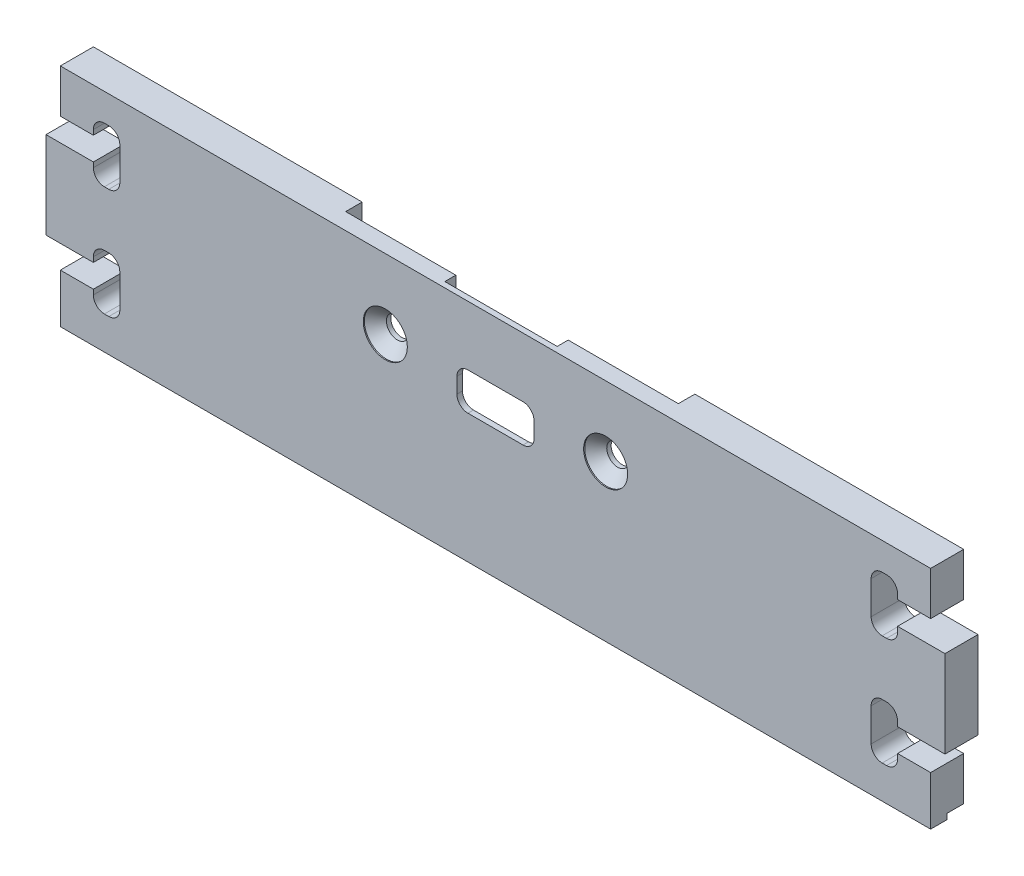
SolidWorks part; units mm, degrees
ref_plane "Front Plane" through (0, 0, 0) normal (0, 0, 1) x (1, 0, 0)
ref_plane "Top Plane" through (0, 0, 0) normal (0, 1, 0) x (1, 0, 0)
ref_plane "Right Plane" through (0, 0, 0) normal (1, 0, 0) x (0, 0, -1)
sketch "Sketch1" plane through (0, 0, 0) normal (0, 0, 1) x (1, 0, 0)
  line L0 (-39.5, 0) -> (39.5, 0) construction
  line L1 (-39.5, 10) -> (39.5, 10)
  line L2 (-39.5, 10) -> (-39.5, -10)
  line L3 (-39.5, -10) -> (39.5, -10)
  line L4 (39.5, 10) -> (39.5, -10)
  line L5 (-39.5, 10) -> (39.5, -10) construction
  line L6 (-39.5, -10) -> (39.5, 10) construction
  line L7 (0, 10) -> (0, -10) construction
  line L9 (-40.8, -3.95) -> (-39.5, -3.95)
  line L10 (-40.8, -3.95) -> (-40.8, 3.95)
  line L11 (-40.8, 3.95) -> (-39.5, 3.95)
  line L12 (-39.5, -3.95) -> (-39.5, 3.95)
  line L13 (-40.8, -3.95) -> (-39.5, 3.95) construction
  line L14 (-40.8, 3.95) -> (-39.5, -3.95) construction
  line L16 (40.8, 3.95) -> (39.5, 3.95)
  line L17 (40.8, -3.95) -> (40.8, 3.95)
  line L18 (40.8, -3.95) -> (39.5, -3.95)
  line L19 (-39.5, 5) -> (39.5, 5) construction
  line L20 (-35.3, 7.5) -> (-35.3, 2.5) construction
  line L21 (-36.5, 3.95) -> (-39.5, 3.95)
  line L22 (-36.5, 3.95) -> (-36.5, 6.05)
  line L23 (-36.5, 6.05) -> (-39.5, 6.05)
  line L24 (-39.5, 3.95) -> (-39.5, 6.05)
  line L25 (-36.5, 3.95) -> (-39.5, 6.05) construction
  line L26 (-36.5, 6.05) -> (-39.5, 3.95) construction
  line L27 (-34.1, 7.5) -> (-36.5, 7.5)
  line L28 (-34.1, 7.5) -> (-34.1, 2.5)
  line L29 (-34.1, 2.5) -> (-36.5, 2.5)
  line L30 (-36.5, 7.5) -> (-36.5, 2.5)
  line L31 (-34.1, 7.5) -> (-36.5, 2.5) construction
  line L32 (-34.1, 2.5) -> (-36.5, 7.5) construction
  line L33 (-34.1, -7.5) -> (-36.5, -7.5)
  line L34 (-34.1, -7.5) -> (-34.1, -2.5)
  line L35 (-34.1, -2.5) -> (-36.5, -2.5)
  line L36 (-36.5, -7.5) -> (-36.5, -2.5)
  line L37 (-36.5, -3.95) -> (-39.5, -3.95)
  line L38 (-36.5, -6.05) -> (-39.5, -6.05)
  line L39 (36.5, 3.95) -> (39.5, 3.95)
  line L40 (36.5, 6.05) -> (39.5, 6.05)
  line L41 (36.5, 7.5) -> (36.5, 2.5)
  line L42 (34.1, 7.5) -> (36.5, 7.5)
  line L43 (34.1, 7.5) -> (34.1, 2.5)
  line L44 (34.1, 2.5) -> (36.5, 2.5)
  line L45 (34.1, -2.5) -> (36.5, -2.5)
  line L46 (34.1, -7.5) -> (34.1, -2.5)
  line L47 (34.1, -7.5) -> (36.5, -7.5)
  line L48 (36.5, -7.5) -> (36.5, -2.5)
  line L49 (36.5, -6.05) -> (39.5, -6.05)
  line L50 (36.5, -3.95) -> (39.5, -3.95)
  point P0 (0, 0)
  point P10 (-40.15, 0)
  point P15 (-38, 5)
  point P35 (-35.3, 5)
  dimension "D1" = 79
  dimension "D2" = 20
  dimension "D4" = 1.3
  dimension "D7" = 5
  dimension "D8" = 2.1
  dimension "D9" = 3
  dimension "D10" = 2.4
  dimension "D11" = 5
extrude "Base shape" add sketch "Sketch1" along normal blind 3 contours L4 L1 L2 L3 | L9 L2 L11 L10 | L16 L4 L18 L17 region at (0, 0, 0) region at (-40.15, 0, 0) region at (40.15, 0, 0)
sketch "Sketch4" plane through (0, -10, 0) normal (0, -1, 0) x (1, 0, 0)
  line L0 (39.5, 3) -> (39.5, 0) construction
  line L1 (-39.5, 3) -> (39.5, 3)
  line L2 (-39.5, 3) -> (-39.5, 1.5)
  line L3 (-39.5, 1.5) -> (39.5, 1.5)
  line L4 (39.5, 3) -> (39.5, 1.5)
extrude "Floor lip" add sketch "Sketch4" along normal blind 0.5
sketch "Sketch6" plane through (0, 0, 0) normal (0, 0, -1) x (-1, 0, 0)
  line L0 (0, 0) -> (0, -10) construction
  line L1 (39.5, -10) -> (-39.5, -10) construction
  line L2 (-4, -10) -> (4, -10) construction
  line L3 (39.5, -10) -> (-39.5, -10) construction
  line L4 (-4, -9) -> (4, -9)
  line L5 (-4, -11) -> (4, -11)
  arc A0 (-4, -9) -> (-4, -11) centre (-4, -10) ccw
  arc A1 (4, -11) -> (4, -9) centre (4, -10) ccw
  point P9 (0, -10)
  dimension "D1" = 2
  dimension "D2" = 8
extrude "Nail cutout" cut sketch "Sketch6" against normal up to surface (1.5 mm away) up to face at (0, -10.25, 1.5)
sketch "Sketch3" plane through (-40.8, 0, 0) normal (-1, 0, 0) x (0, 0, 1)
  line L0 (0, 6.05) -> (3, 3.95) construction
  line L1 (0, 6.05) -> (3, 6.05)
  line L2 (0, 6.05) -> (0, 3.95)
  line L3 (0, 3.95) -> (3, 3.95)
  line L4 (3, 6.05) -> (3, 3.95)
  line L5 (0, -3.95) -> (3, -6.05) construction
  line L6 (0, -3.95) -> (3, -3.95)
  line L7 (0, -3.95) -> (0, -6.05)
  line L8 (0, -6.05) -> (3, -6.05)
  line L9 (3, -3.95) -> (3, -6.05)
  point P6 (1.5, 5)
  point P13 (1.5, -5)
ref_axis "Tap axis top" through (-53.7846, 5, 1.5) along (1, 0, 0)
ref_axis "Tap axis bottom" through (-54.2844, -5, 1.5) along (1, 0, 0)
fillet "Mill fillets" radius 1 16 edges at (36.5, -7.5, 1.5) (36.5, 2.5, 1.5) (34.1, 2.5, 1.5) (34.1, -7.5, 1.5) (36.5, -2.5, 1.5) (36.5, 7.5, 1.5) (34.1, -2.5, 1.5) (34.1, 7.5, 1.5) (-36.5, -2.5, 1.5) (-34.1, -2.5, 1.5) (-34.1, -7.5, 1.5) (-36.5, -7.5, 1.5) (-36.5, 2.5, 1.5) (-34.1, 2.5, 1.5) (-34.1, 7.5, 1.5) (-36.5, 7.5, 1.5)
sketch "Sketch8" [suppressed] plane through (0, 0, 3) normal (0, 0, 1) x (1, 0, 0)
  line L0 (-40.8, 0) -> (40.8, 0) construction
  line L1 (-40.8, -3.95) -> (-40.8, 3.95) construction
  line L2 (40.8, -3.95) -> (40.8, 3.95) construction
  line L4 (-24.5, 5.15) -> (24.5, 5.15)
  line L5 (-25.5, 4.15) -> (-25.5, -4.15)
  line L6 (-24.5, -5.15) -> (24.5, -5.15)
  line L7 (25.5, 4.15) -> (25.5, -4.15)
  line L8 (-25.5, 5.15) -> (25.5, -5.15) construction
  line L9 (-25.5, -5.15) -> (25.5, 5.15) construction
  arc A0 (24.5, -5.15) -> (25.5, -4.15) centre (24.5, -4.15) ccw
  arc A1 (24.5, 5.15) -> (25.5, 4.15) centre (24.5, 4.15) cw
  arc A2 (-25.5, -4.15) -> (-24.5, -5.15) centre (-24.5, -4.15) ccw
  arc A3 (-24.5, 5.15) -> (-25.5, 4.15) centre (-24.5, 4.15) ccw
  point P6 (0, 0)
  dimension "D3" = 1
  dimension "D1" = 51
  dimension "D2" = 10.3
extrude "Led strip pocket" [suppressed] cut sketch "Sketch8" against normal offset from surface (2.5 mm away) 0.5 up to face at (0, -0.6712, 0)
sketch "Sketch9" [suppressed] plane through (0, 0, 0.5) normal (0, 0, 1) x (1, 0, 0)
  line L0 (-19.5, 5.15) -> (-19.5, -5.15)
  line L1 (0, 5.15) -> (0, -5.15) construction
  line L2 (19.5, 5.15) -> (19.5, -5.15)
  line L3 (-25.5, -2.978) -> (25.5, -2.978) construction
  line L4 (25.5, -4.15) -> (25.5, 4.15)
  line L5 (24.5, 5.15) -> (-24.5, 5.15)
  line L6 (-25.5, 4.15) -> (-25.5, -4.15)
  line L7 (-24.5, -5.15) -> (24.5, -5.15)
  line L8 (25.5, -4.15) -> (25.5, 4.15)
  line L9 (24.5, 5.15) -> (-24.5, 5.15)
  line L10 (-25.5, 4.15) -> (-25.5, -4.15)
  line L11 (-24.5, -5.15) -> (24.5, -5.15)
  circle A0 centre (-12.7, -2.978) radius 1
  circle A1 centre (12.7, -2.978) radius 1
  arc A4 (24.5, -5.15) -> (25.5, -4.15) centre (24.5, -4.15) ccw
  arc A5 (25.5, 4.15) -> (24.5, 5.15) centre (24.5, 4.15) ccw
  arc A6 (-24.5, 5.15) -> (-25.5, 4.15) centre (-24.5, 4.15) ccw
  arc A7 (-25.5, -4.15) -> (-24.5, -5.15) centre (-24.5, -4.15) ccw
  arc A8 (24.5, -5.15) -> (25.5, -4.15) centre (24.5, -4.15) ccw
  arc A9 (25.5, 4.15) -> (24.5, 5.15) centre (24.5, 4.15) ccw
  arc A10 (-24.5, 5.15) -> (-25.5, 4.15) centre (-24.5, 4.15) ccw
  arc A11 (-25.5, -4.15) -> (-24.5, -5.15) centre (-24.5, -4.15) ccw
  arc M13 (24.5, -5.15) -> (25.5, -4.15) centre (24.5, -4.15) ccw
  line M14 (25.5, -4.15) -> (25.5, 4.15)
  arc M15 (25.5, 4.15) -> (24.5, 5.15) centre (24.5, 4.15) ccw
  line M16 (24.5, 5.15) -> (-24.5, 5.15)
  arc M17 (-24.5, 5.15) -> (-25.5, 4.15) centre (-24.5, 4.15) ccw
  line M18 (-25.5, 4.15) -> (-25.5, -4.15)
  arc M19 (-25.5, -4.15) -> (-24.5, -5.15) centre (-24.5, -4.15) ccw
  line M20 (-24.5, -5.15) -> (24.5, -5.15)
  dimension "D4" = 2
  dimension "D2" = 6
  dimension "D3" = 8.128
  dimension "D5" = 25.4
  dimension "D1" = 0
extrude "Led strip cuts" [suppressed] cut sketch "Sketch9" against normal up to next contours L0 M16 M17 M18 M19 M20 | L2 M16 M20 M13 M14 M15 | A0 | A1
fillet "Led strip cut fillets" [suppressed] radius 1
sketch "Sketch13" plane through (0, 0, 0) normal (0, 0, -1) x (-1, 0, 0)
  line L0 (0, 15.8648) -> (0, -21.9195) construction
  line L2 (-4.1, -2.7) -> (4.1, -2.7)
  line L3 (-5.1, -1.7) -> (-5.1, 10)
  line L4 (-5.1, 10) -> (5.1, 10)
  line L5 (5.1, -1.7) -> (5.1, 10)
  line L6 (-5.1, -2.7) -> (5.1, 10) construction
  line L7 (-5.1, 10) -> (5.1, -2.7) construction
  line L9 (39.5, 10) -> (-39.5, 10) construction
  arc A0 (-4.1, -2.7) -> (-5.1, -1.7) centre (-4.1, -1.7) cw
  arc A1 (4.1, -2.7) -> (5.1, -1.7) centre (4.1, -1.7) ccw
  point P1 (0, 3.65)
  point P8 (0, 0)
  point P9 (5.5684, 9.0125)
  point P16 (0, 0)
  point P17 (0, 0)
  dimension "D4" = 1
  dimension "D1" = 10.2
  dimension "D2" = 12.7
extrude "Bumper mount inner cut" cut sketch "Sketch13" against normal offset from surface (2.5 mm away) 0.5 up to face at (0, -0.0192, 3)
sketch "Sketch14" plane through (0, 0, 0) normal (0, 0, -1) x (-1, 0, 0)
  line L0 (5.1, 10) -> (-5.1, 10) construction
  line L1 (0, 12.9528) -> (0, -14.0841) construction
  line L3 (-4.1, -2.7) -> (4.1, -2.7) construction
  line L4 (-15.1, 10) -> (15.1, 10)
  line L5 (-15.1, 10) -> (-15.1, -1.7)
  line L6 (-14.1, -2.7) -> (14.1, -2.7)
  line L7 (15.1, 10) -> (15.1, -1.7)
  line L8 (-15.1, 10) -> (15.1, -2.7) construction
  line L9 (-15.1, -2.7) -> (15.1, 10) construction
  arc A1 (14.1, -2.7) -> (15.1, -1.7) centre (14.1, -1.7) ccw
  arc A2 (-15.1, -1.7) -> (-14.1, -2.7) centre (-14.1, -1.7) ccw
  point P6 (0, 3.65)
  dimension "D2" = 1
  dimension "D1" = 30.2
extrude "Bumper mount outer cut" cut sketch "Sketch14" against normal blind 1.5
sketch "Sketch15" plane through (0, 0, 1.5) normal (0, 0, -1) x (-1, 0, 0)
  line L0 (-15.1, 3.65) -> (15.1, 3.65) construction
  line L3 (0, 16.4744) -> (0, -20.0474) construction
  line L4 (10.1, 10) -> (10.1, -2.7) construction
  line L5 (15.1, 10) -> (5.1, 10) construction
  line L6 (-14.1, -2.7) -> (14.1, -2.7) construction
  line L7 (-15.1, 10) -> (-15.1, -1.7) construction
  line L8 (15.1, -1.7) -> (15.1, 10) construction
  circle A0 centre (-10, 3.65) radius 1
  circle A1 centre (10, 3.65) radius 1
  point P2 (10.1, 3.65)
  point P13 (0, 0)
  point P19 (0, 0)
  dimension "D1" = 20
  dimension "D2" = 2
extrude "Bumper mount screw holes" cut sketch "Sketch15" against normal up to next
sketch "Sketch16" plane through (0, 0, 2.5) normal (0, 0, -1) x (-1, 0, 0)
  line L0 (-5.1, 2.9) -> (5.1, 2.9) construction
  line L3 (0, 10) -> (0, -4.2) construction
  line L4 (-2.5, 4.6) -> (2.5, 4.6)
  line L5 (-3.5, 3.6) -> (-3.5, 2.2)
  line L6 (-2.5, 1.2) -> (2.5, 1.2)
  line L7 (3.5, 3.6) -> (3.5, 2.2)
  line L8 (-3.5, 4.6) -> (3.5, 1.2) construction
  line L9 (-3.5, 1.2) -> (3.5, 4.6) construction
  line L11 (-5.1, 10) -> (-5.1, -1.7) construction
  line L12 (5.1, 10) -> (-5.1, 10) construction
  arc A0 (2.5, 1.2) -> (3.5, 2.2) centre (2.5, 2.2) ccw
  arc A1 (-3.5, 2.2) -> (-2.5, 1.2) centre (-2.5, 2.2) ccw
  arc A2 (-2.5, 4.6) -> (-3.5, 3.6) centre (-2.5, 3.6) ccw
  arc A3 (2.5, 4.6) -> (3.5, 3.6) centre (2.5, 3.6) cw
  point P2 (0, 0)
  point P5 (0, 0)
  point P6 (0, 2.9)
  point P23 (0, 0)
  dimension "D3" = 1
  dimension "D1" = 7
  dimension "D2" = 3.4
  dimension "D4" = 14.2
extrude "Bumper body cut" cut sketch "Sketch16" against normal up to next
hole_wizard "Bumper screw countersunks" positions "Sketch17" profile "Sketch18" countersink size "M2" standard "ANSI Metric" end condition through all
sketch "Sketch17" plane through (0, 0, 3) normal (0, 0, 1) x (1, 0, 0)
  point P0 (10, 3.65)
  point P3 (-10, 3.65)
sketch "Sketch18" plane through (10, 3.65, 3) normal (1, 0, 0) x (0, -1, 0)
  line L0 (0, 0) -> (0, 3)
  line L1 (0, 3) -> (1, 3)
  line L2 (1, 3) -> (1, 1.1)
  line L3 (1, 1.1) -> (2, 0.1)
  line L4 (2, 0.1) -> (2, 0)
  line L6 (2, 0) -> (0, 0)
  line L7 (-1, 1.1) -> (-2, 0.1) construction
  line L11 (0, -6.35) -> (0, 107.95) construction
  dimension "Thru Hole Dia." = 2
  dimension "Thru Hole Depth" = 3
  dimension "C'Sink Dia." = 4
  dimension "C'Sink Angle" = 90
  dimension "Head Clearance" = 0.1
